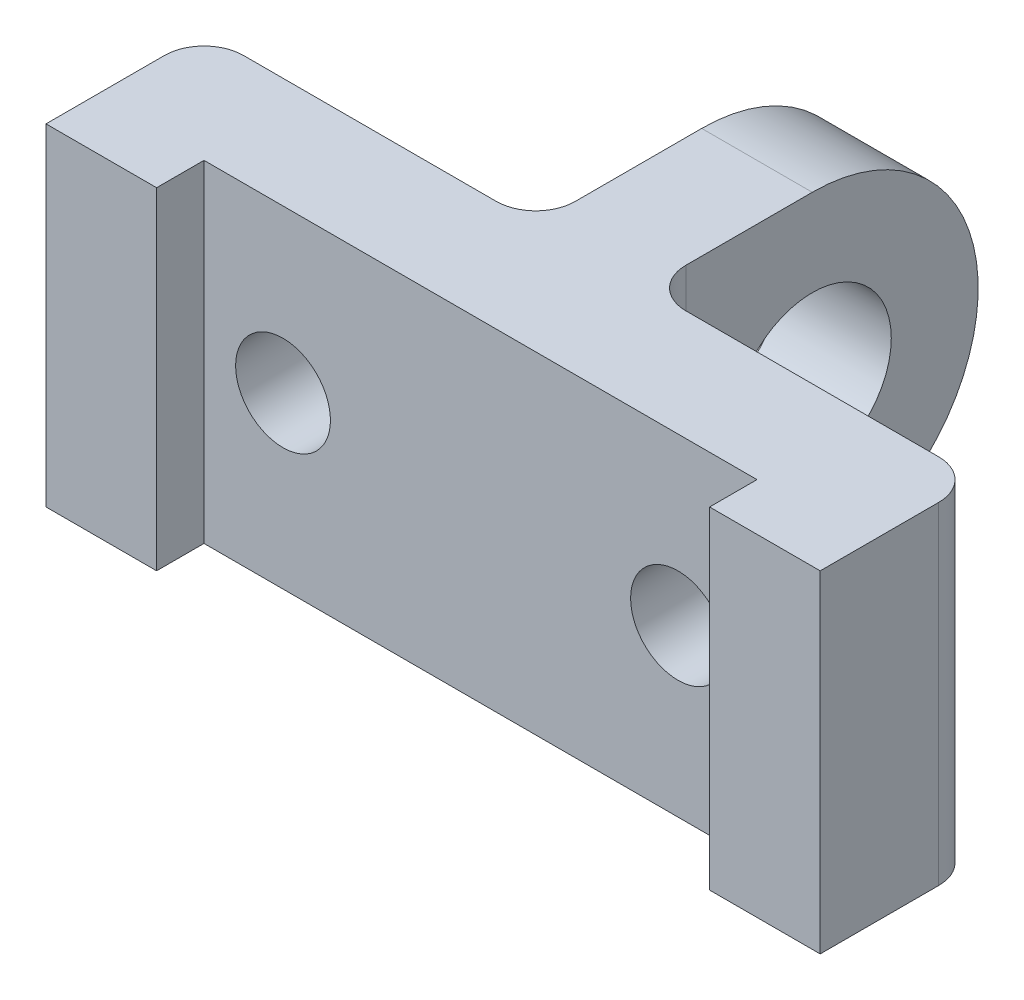
SolidWorks part; units mm, degrees
ref_plane "Front Plane" through (0, 0, 0) normal (0, 0, 1) x (1, 0, 0)
ref_plane "Top Plane" through (0, 0, 0) normal (0, 1, 0) x (1, 0, 0)
ref_plane "Right Plane" through (0, 0, 0) normal (1, 0, 0) x (0, 0, -1)
sketch "Sketch1" plane through (0, 0, 0) normal (0, 0, 1) x (1, 0, 0)
  line L0 (-76.7682, 0) -> (82.651, 0) construction
  line L1 (0, 59.2001) -> (0, -69.764) construction
  line L3 (-49, -21) -> (49, -21)
  line L4 (-49, -21) -> (-49, 21)
  line L5 (-49, 21) -> (49, 21)
  line L6 (49, -21) -> (49, 21)
  line L7 (-49, -21) -> (49, 21) construction
  line L8 (-49, 21) -> (49, -21) construction
  point P10 (0, 0)
  dimension "D1" = 98
  dimension "D2" = 42
extrude "Boss-Extrude1" add sketch "Sketch1" along normal blind 14
sketch "Sketch3" plane through (0, 0, 0) normal (0, 0, 1) x (1, 0, 0)
  line L0 (25, 0) -> (-65.7177, 0) construction
  line L1 (25, 0) -> (63.2181, 0) construction
  line L2 (0, 33.1713) -> (0, -32.7547) construction
  line L3 (-25, 14.8701) -> (-25, -13.8723) construction
  line L4 (25, 15.7786) -> (25, -12.1306) construction
  line L6 (49, -21) -> (49, 21) construction
  line L7 (-49, 21) -> (-49, -21) construction
  circle A0 centre (-25, 0.4989) radius 6
  circle A1 centre (25, 0) radius 6
  dimension "D1" = 12
  dimension "D2" = 12
  dimension "D3" = 24
  dimension "D4" = 24
extrude "Cut-Extrude1" cut sketch "Sketch3" along normal blind 31 contours A1
extrude "Cut-Extrude2" cut sketch "Sketch3<3>" along normal blind 150
sketch "Sketch3<3>" plane through (0, 0, 0) normal (0, 0, 1) x (1, 0, 0) same geometry as "Sketch3"
fillet "Fillet1" radius 5 1 edges at (-49, 0, 0)
sketch "Sketch4" plane through (0, 0, 14) normal (0, 0, 1) x (1, 0, 0)
  line L0 (49, 21) -> (-49, 21) construction
  line L1 (-49, -21) -> (-35, -21)
  line L2 (-49, -21) -> (-49, 21)
  line L3 (-49, 21) -> (-35, 21)
  line L4 (-35, -21) -> (-35, 21)
  dimension "D1" = 14
extrude "Boss-Extrude2" add sketch "Sketch4" along normal blind 6
fillet "Fillet2" radius 5 1 edges at (49, 0, 0)
sketch "Sketch5" plane through (0, 0, 14) normal (0, 0, 1) x (1, 0, 0)
  line L0 (49, 21) -> (-35, 21) construction
  line L1 (49, -21) -> (35, -21)
  line L2 (49, -21) -> (49, 21)
  line L3 (49, 21) -> (35, 21)
  line L4 (35, -21) -> (35, 21)
  dimension "D1" = 14
extrude "Boss-Extrude3" add sketch "Sketch5" along normal blind 6
sketch "Sketch6" plane through (0, 0, 0) normal (1, 0, 0) x (0, 0, -1)
  line L1 (0, 21) -> (42, 21)
  line L2 (0, 21) -> (0, -21)
  line L3 (0, -21) -> (42, -21)
  line L4 (42, 21) -> (42, -21)
  dimension "D1" = 42
  dimension "D2" = 42
extrude "Boss-Extrude4" add sketch "Sketch6" along normal mid plane 14
fillet "Fillet4" 2 edges at (0, 21, -42) (0, -21, -42) type full round first side face at (0, 21, 2.2806) second side face at (0, -21, 2.2806) middle face at (0, 0, -42)
sketch "Sketch7" plane through (0, 0, 0) normal (1, 0, 0) x (0, 0, -1)
  circle A0 centre (21, 0) radius 10
  dimension "D1" = 20
  dimension "D2" = 21
extrude "Cut-Extrude3" cut sketch "Sketch7" along normal mid plane 41
fillet "Fillet5" radius 5 2 edges at (7, 0, 0) (-7, 0, 0)
